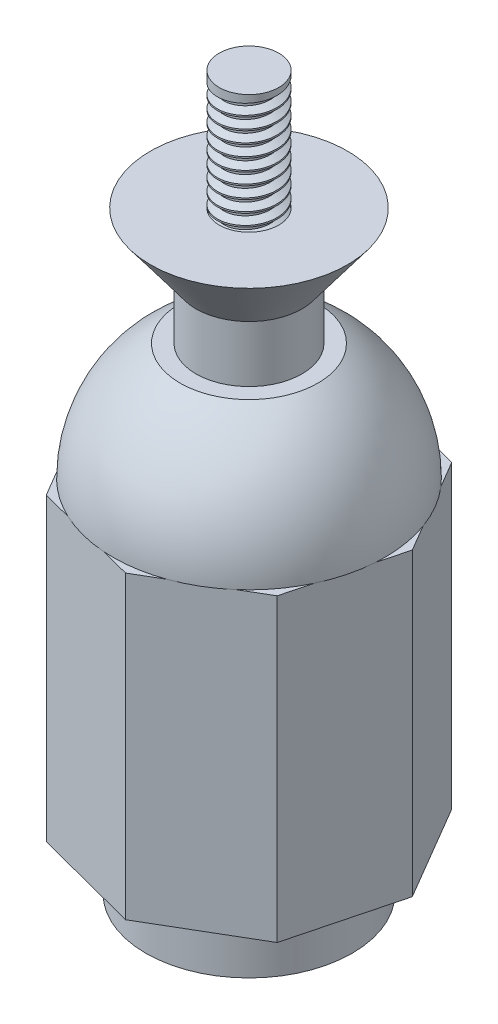
SolidWorks part; units mm, degrees
ref_plane "Front Plane" through (0, 0, 0) normal (0, 0, 1) x (1, 0, 0)
ref_plane "Top Plane" through (0, 0, 0) normal (0, 1, 0) x (1, 0, 0)
ref_plane "Right Plane" through (0, 0, 0) normal (1, 0, 0) x (0, 0, -1)
sketch "Sketch1" plane through (0, 0, 0) normal (0, 1, 0) x (1, 0, 0)
  circle A0 centre (0, 0) radius 11
  dimension "D1" = 22
extrude "Boss-Extrude1" add sketch "Sketch1" along normal blind 6.3
sketch "Sketch2" plane through (0, 6.3, 0) normal (0, 1, 0) x (1, 0, 0)
  line L1 (-2.1253, 15.277) -> (-12.3052, 9.2997)
  line L2 (-12.3052, 9.2997) -> (-15.277, -2.1253)
  line L3 (-15.277, -2.1253) -> (-9.2997, -12.3052)
  line L4 (-9.2997, -12.3052) -> (2.1253, -15.277)
  line L5 (2.1253, -15.277) -> (12.3052, -9.2997)
  line L6 (12.3052, -9.2997) -> (15.277, 2.1253)
  line L7 (15.277, 2.1253) -> (9.2997, 12.3052)
  line L8 (9.2997, 12.3052) -> (-2.1253, 15.277)
  circle A0 centre (0, 0) radius 14.25 construction
  dimension "D1" = 28.5
extrude "Boss-Extrude2" add sketch "Sketch2" along normal blind 32 contours L1 L2 L3 L4 L5 L6 L7 L8
sketch "Sketch3" plane through (0, 0, 0) normal (0, 0, 1) x (1, 0, 0)
  line L0 (0, 52.8) -> (0, 38.3)
  line L1 (9.2997, 38.3) -> (-2.1253, 38.3) construction
  line L2 (-14.5, 38.3) -> (0, 38.3)
  arc A0 (0, 52.8) -> (-14.5, 38.3) centre (0, 38.3) ccw
  dimension "D1" = 29
revolve "Revolve2" add sketch "Sketch3" angle 360 about L0
sketch "Sketch4" plane through (0, 0, 0) normal (0, 0, 1) x (1, 0, 0)
  line L0 (-6.1818, 38.3) -> (-0.9926, 38.3) construction
  line L1 (-15.1792, 53.8) -> (15.505, 53.8)
  line L2 (-15.1792, 53.8) -> (-15.1792, 50.8)
  line L3 (-15.1792, 50.8) -> (15.505, 50.8)
  line L4 (15.505, 53.8) -> (15.505, 50.8)
  dimension "D1" = 12.5
  dimension "D2" = 3
extrude "Cut-Extrude1" cut sketch "Sketch4" against normal blind 32 and the other way blind 32
sketch "Sketch5" plane through (0, 50.8, 0) normal (0, 1, 0) x (1, 0, 0)
  circle A0 centre (0, 0) radius 5.65
  dimension "D1" = 11.3
extrude "Boss-Extrude3" add sketch "Sketch5" along normal blind 6
sketch "Sketch6" plane through (0, 0, 0) normal (1, 0, 0) x (0, 0, -1)
  line L0 (0, 63.3) -> (0, 56.8)
  line L1 (5.65, 56.8) -> (-5.65, 56.8) construction
  line L2 (0, 63.3) -> (10.5, 63.3)
  line L3 (10.5, 63.3) -> (5.65, 56.8)
  line L4 (5.65, 56.8) -> (0, 56.8)
  dimension "D1" = 6.5
  dimension "D2" = 10.5
revolve "Revolve3" add sketch "Sketch6" angle 360 about L0
sketch "Sketch7" plane through (0, 63.3, 0) normal (0, 1, 0) x (1, 0, 0)
  circle A0 centre (0, 0) radius 3.175
  dimension "D1" = 6.35
extrude "Boss-Extrude4" add sketch "Sketch7" along normal blind 12.7
sketch "Sketch8" plane through (0, 0, 0) normal (0, -1, 0) x (-1, 0, 0)
  circle A0 centre (0, 0) radius 3.175
  dimension "D1" = 6.35
extrude "Cut-Extrude2" cut sketch "Sketch8" against normal blind 17.78
thread "Thread1" pitch 1.27 method extrude profile "Thread Profile1" start angle 0, offset 0, length 17.78, pitch 1.27, diameter 6.35
ref_plane "Plane1" through (3.175, 0, 0) normal (0, 0, 1) x (1, 0, 0)
sketch "Thread Profile1" plane through (3.175, 0, 0) normal (0, 0, 1) x (1, 0, 0)
  line L0 (0, 0) -> (0, 1.27) construction
  line L11 (0, 0) -> (0, 1.1112)
  line L12 (0, 1.1112) -> (-0.6874, 0.7144)
  line L13 (-0.6874, 0.7144) -> (-0.6874, 0.3969)
  line L15 (-0.6874, 0.3969) -> (0, 0)
  line L17 (-0.6874, 0.5556) -> (0, 0.5556) construction
  point P2 (0, 0)
  dimension "Pitch" = 1.27
  dimension "Profile_Angle" = 60
  dimension "Profile_Land" = 0.3175
  dimension "Profile_Height" = 0.6874
thread "Thread2" pitch 1.27 method cut profile "Thread Profile2" start angle 0, offset 0, length 0, pitch 1.27, diameter 6.35
ref_plane "Plane2" through (-3.175, 76, 0) normal (0, 0, 1) x (-1, 0, 0)
sketch "Thread Profile2" plane through (-3.175, 76, 0) normal (0, 0, 1) x (-1, 0, 0)
  line L0 (0, 0) -> (0, 1.27) construction
  line L11 (0, 0) -> (0, 1.1112)
  line L12 (0, 1.1112) -> (-0.6874, 0.7144)
  line L13 (-0.6874, 0.7144) -> (-0.6874, 0.3969)
  line L15 (-0.6874, 0.3969) -> (0, 0)
  line L17 (-0.6874, 0.5556) -> (0, 0.5556) construction
  point P2 (0, 0)
  dimension "Pitch" = 1.27
  dimension "Profile_Angle" = 60
  dimension "Profile_Land" = 0.3175
  dimension "Profile_Height" = 0.6874
